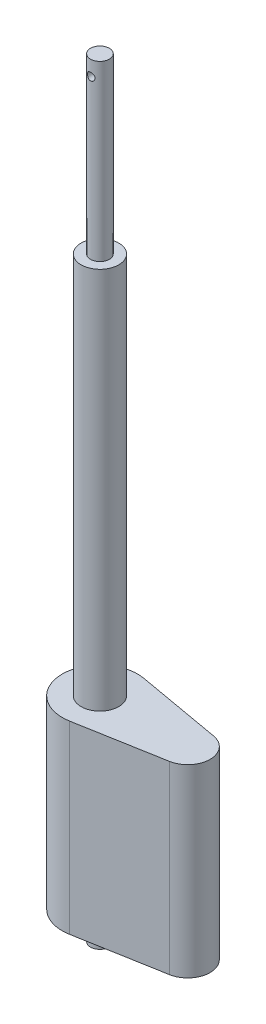
SolidWorks part; units mm, degrees
ref_plane "Front" through (0, 0, 0) normal (0, 0, 1) x (1, 0, 0)
ref_plane "Top" through (0, 0, 0) normal (0, 1, 0) x (1, 0, 0)
ref_plane "Right" through (0, 0, 0) normal (1, 0, 0) x (0, 0, -1)
sketch "Sketch7" plane through (0, 0, 0) normal (1, 0, 0) x (0, 0, -1)
  line L1 (-20, 7) -> (-20, 105)
  line L4 (-10, 308) -> (-5, 308)
  line L5 (-5, 308) -> (-5, 400)
  line L6 (-5, 400) -> (0, 400)
  line L7 (0, 400) -> (0, -8)
  line L9 (-5, -8) -> (0, -8)
  line L10 (-10, 308) -> (-10, 105)
  line L11 (-10, 105) -> (-20, 105)
  line L12 (-5, -8) -> (-5, 7)
  line L13 (-5, 7) -> (-20, 7)
  point P11 (0, 0)
  point P12 (0, 392)
  point P13 (0, 320)
  dimension "D1" = 8
  dimension "D2" = 8
  dimension "D3" = 98
  dimension "D5" = 12
  dimension "D7" = 10
  dimension "D8" = 20
  dimension "D11" = 5
  dimension "D9" = 15
  dimension "D10" = 5
  dimension "D4" = 80
  dimension "D6" = 320
revolve "Revolve2" add sketch "Sketch7" angle 360 about L7
sketch "Sketch8" plane through (0, 0, 0) normal (0, 0, 1) x (1, 0, 0)
  line L0 (-5, -8) -> (5, -8) construction
  line L2 (0, 400) -> (0, 392) construction
  line L3 (5, 400) -> (-5, 400) construction
  line L4 (-5, -8) -> (5, -8) construction
  line L5 (0, -8) -> (0, 0) construction
  circle A1 centre (0, 392) radius 2
  circle A2 centre (0, 0) radius 2
  dimension "D2" = 8
  dimension "D1" = 4
  dimension "D4" = 4
  dimension "D3" = 8
extrude "Cut-Extrude2" cut sketch "Sketch8" against normal through all and the other way through all
sketch "Sketch10" plane through (0, 105, 0) normal (0, 1, 0) x (1, 0, 0)
  line L0 (0, 0) -> (46.5567, 0) construction
  line L1 (3.491, 19.693) -> (48.6292, 11.6912)
  line L2 (48.6292, -11.6912) -> (3.491, -19.693)
  circle A1 centre (0, 0) radius 20 construction
  arc A2 (48.6292, 11.6912) -> (48.6292, -11.6912) centre (46.5567, 0) cw
  arc A3 (3.491, 19.693) -> (3.491, -19.693) centre (0, 0) ccw
extrude "Boss-Extrude4" add sketch "Sketch10" against normal up to surface (98 mm away) up to face at (0, 7, 5)
sketch "Sketch11" plane through (0, 0, 0) normal (0, 0, 1) x (1, 0, 0)
  line L0 (0, 392) -> (0, 0)
equation "\"mountingHoleDistance\"=8"
equation "\"actuatorLength\"=80"
equation "\"D1@Sketch7\"= \"mountingHoleDistance\""
equation "\"D2@Sketch7\"=\"mountingHoleDistance\""
equation "\"MotorHousingHeight\"= 98"
equation "\"D3@Sketch7\"=\"MotorHousingHeight\""
equation "\"acutatorMinimumLength\"= 320"
equation "\"D3@Sketch8\"=\"mountingHoleDistance\""
equation "\"D2@Sketch8\"=\"mountingHoleDistance\""
equation "\"D4@Sketch7\"=\"actuatorLength\""
equation "\"D6@Sketch7\"=\"acutatorMinimumLength\""
